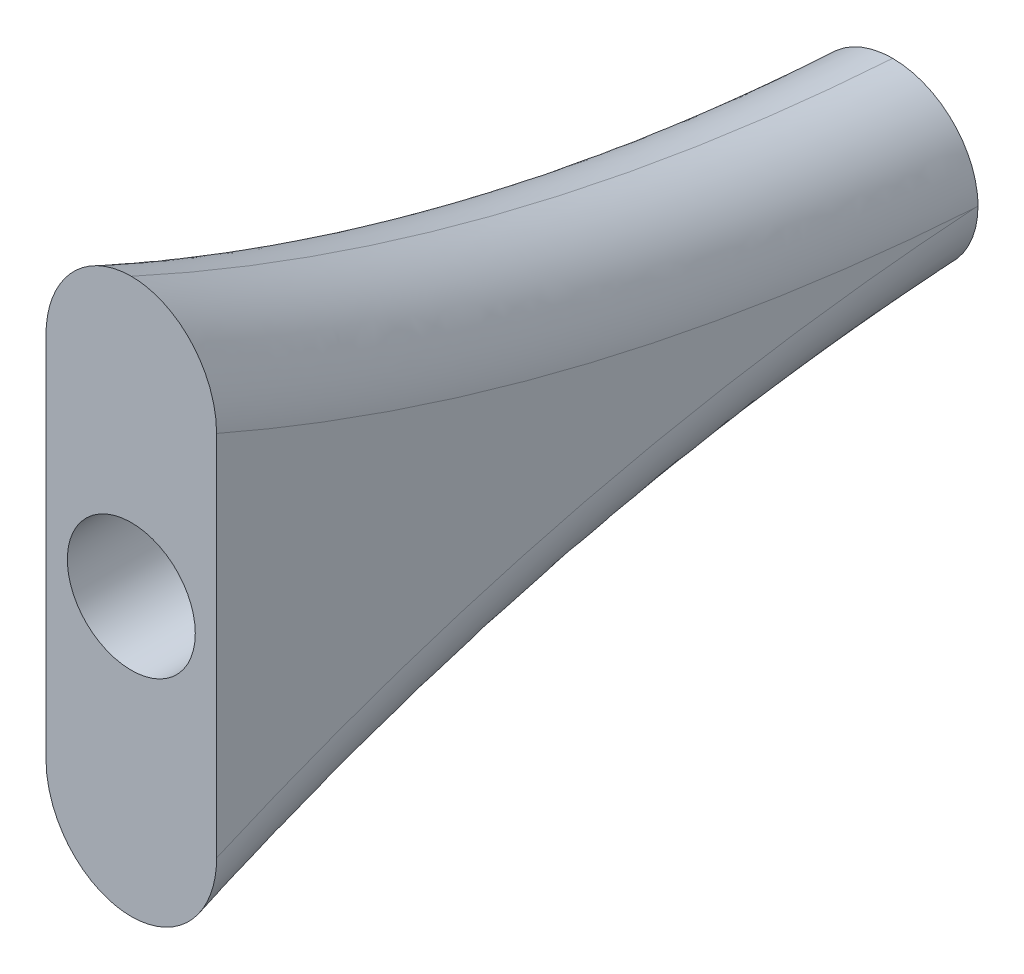
SolidWorks part; units mm, degrees
ref_plane "Front Plane" through (0, 0, 0) normal (0, 0, 1) x (1, 0, 0)
ref_plane "Top Plane" through (0, 0, 0) normal (0, 1, 0) x (1, 0, 0)
ref_plane "Right Plane" through (0, 0, 0) normal (1, 0, 0) x (0, 0, -1)
sketch "Sketch1" plane through (0, 0, 0) normal (1, 0, 0) x (0, 0, -1)
  line L0 (0, 93.3577) -> (0, -108.9715) construction
  line L2 (178.5, 0) -> (0, 0) construction
  line L3 (0, 65) -> (0, -65)
  line L4 (178.5, 10) -> (69.5866, 10) construction
  line L5 (69.5866, 10) -> (69.5866, 39.0825) construction
  line L6 (69.5866, 39.0825) -> (22.462, 39.0825) construction
  line L7 (22.462, 39.0825) -> (22.462, 55.3579) construction
  line L9 (178.5, -20) -> (178.5, 20)
  line L10 (0, -20) -> (69.5866, -20) construction
  line L12 (69.5866, -20) -> (69.5866, -39.0826) construction
  line L13 (69.5866, -20) -> (123.4263, -20) construction
  line L14 (123.4263, -20) -> (123.4263, -26.5927) construction
  line L15 (78.2907, 36.636) -> (78.2907, -36.636) construction
  spline S0 degree 2 poles (0, 65) (84.8249, 26.1937) (178.5, 20) knots 0 0 0 1 1 1
  spline S1 degree 2 poles (0, -65) (84.8249, -26.1937) (178.5, -20) knots 0 0 0 1 1 1
  dimension "D4" = 108.9134
  dimension "D9" = 69.5866
  dimension "D7" = 20
  dimension "D1" = 65
  dimension "D2" = 20
  dimension "D3" = 40
  dimension "D5" = 47.1246
  dimension "D6" = 16.2753
  dimension "D8" = 19.0826
  dimension "D10" = 178.5
  dimension "D11" = 73.272
  dimension "D12" = 55.8287
extrude "Boss-Extrude1" add sketch "Sketch1" along normal mid plane 40
sketch "Sketch10" plane through (0, 0, 0) normal (0, 0, 1) x (1, 0, 0)
  circle A0 centre (0, 0) radius 15
  dimension "D1" = 30
extrude "Cut-Extrude1" cut sketch "Sketch10" against normal blind 70
sketch "Sketch11" plane through (0, 0, -178.5) normal (0, 0, -1) x (-1, 0, 0)
  circle A0 centre (0, 0) radius 6
  dimension "D1" = 12
extrude "Cut-Extrude2" cut sketch "Sketch11" against normal blind 40
fillet "Fillet1" radius 20 4 edges
